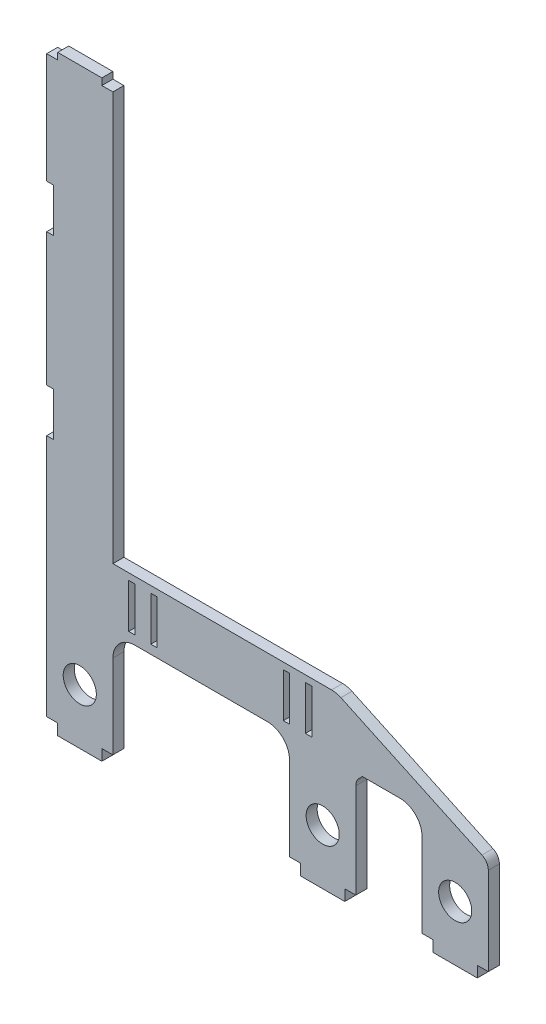
SolidWorks part; units mm, degrees
ref_plane "Front Plane" through (0, 0, 0) normal (0, 0, 1) x (1, 0, 0)
ref_plane "Top Plane" through (0, 0, 0) normal (0, 1, 0) x (1, 0, 0)
ref_plane "Right Plane" through (0, 0, 0) normal (1, 0, 0) x (0, 0, -1)
sketch "Sketch1" plane through (0, 0, 0) normal (0, 0, 1) x (1, 0, 0)
  line L0 (38.6, 72) -> (38.6, 52) construction
  line L1 (48.6, 72) -> (48.6, 52) construction
  line L2 (108.6, 72) -> (108.6, 52) construction
  line L3 (118.6, 72) -> (118.6, 52) construction
  line L4 (155, 62.0711) -> (155, 65.5389)
  line L5 (150.5677, 70.5065) -> (34.4323, 83.7792)
  line L6 (30, 88.7468) -> (30, 260)
  line L7 (30, 260) -> (25, 260)
  line L8 (25, 260) -> (25, 263)
  line L9 (25, 263) -> (5, 263)
  line L10 (5, 263) -> (5, 260)
  line L11 (5, 260) -> (0, 260)
  line L12 (0, 260) -> (0, 0)
  line L13 (0, 0) -> (5, 0)
  line L14 (5, 0) -> (5, -5)
  line L15 (5, -5) -> (25, -5)
  line L16 (25, -5) -> (25, 0)
  line L17 (25, 0) -> (30, 0)
  line L18 (30, 0) -> (30, 40)
  line L19 (35, 45) -> (105, 45)
  line L20 (110, 40) -> (110, 0)
  line L21 (110, 0) -> (115, 0)
  line L22 (115, 0) -> (115, -5)
  line L23 (115, -5) -> (135, -5)
  line L24 (135, -5) -> (135, 0)
  line L25 (135, 0) -> (140, 0)
  line L26 (140, 0) -> (140, 42.9289)
  line L27 (141.4645, 46.4645) -> (153.5355, 58.5355)
  line L28 (40.05, 52) -> (37.15, 52)
  line L29 (40.05, 72) -> (40.05, 52)
  line L30 (37.15, 52) -> (37.15, 72)
  line L31 (37.15, 72) -> (40.05, 72)
  line L32 (47.15, 72) -> (50.05, 72)
  line L33 (47.15, 52) -> (47.15, 72)
  line L34 (50.05, 72) -> (50.05, 52)
  line L35 (50.05, 52) -> (47.15, 52)
  line L36 (117.15, 72) -> (120.05, 72)
  line L37 (120.05, 72) -> (120.05, 52)
  line L38 (120.05, 52) -> (117.15, 52)
  line L39 (117.15, 52) -> (117.15, 72)
  line L40 (110.05, 52) -> (107.15, 52)
  line L41 (110.05, 72) -> (110.05, 52)
  line L42 (107.15, 52) -> (107.15, 72)
  line L43 (107.15, 72) -> (110.05, 72)
  arc A0 (155, 65.5389) -> (150.5677, 70.5065) centre (150, 65.5389) ccw
  arc A1 (30, 88.7468) -> (34.4323, 83.7792) centre (35, 88.7468) ccw
  arc A2 (35, 45) -> (30, 40) centre (35, 40) ccw
  arc A3 (110, 40) -> (105, 45) centre (105, 40) ccw
  arc A4 (141.4645, 46.4645) -> (140, 42.9289) centre (145, 42.9289) ccw
  arc A5 (153.5355, 58.5355) -> (155, 62.0711) centre (150, 62.0711) ccw
  point P63 (39.2533, 51.8883)
  dimension "D20" = 260
  dimension "D21" = 5
  dimension "D23" = 5
  dimension "D24" = 5
  dimension "D25" = 5
  dimension "D26" = 5
  dimension "D27" = 5
  dimension "D1" = 20
  dimension "D2" = 5
  dimension "D3" = 5
  dimension "D4" = 30
  dimension "D5" = 38.6
  dimension "D6" = 10
  dimension "D7" = 110
  dimension "D8" = 5
  dimension "D9" = 20
  dimension "D10" = 30
  dimension "D11" = 108.6
  dimension "D12" = 10
  dimension "D13" = 155
  dimension "D14" = 45
  dimension "D15" = 7
  dimension "D16" = 20
  dimension "D17" = 2.9
  dimension "D18" = 2.9
  dimension "D19" = 6.52
  dimension "D22" = 135
  dimension "D28" = 42.9289
  dimension "D29" = 3.4678
  dimension "D30" = 20
  dimension "D31" = 5
  dimension "D32" = 3
  dimension "D33" = 2.9
  dimension "D34" = 2.9
extrude "Boss-Extrude1" add sketch "Sketch1" along normal blind 5
sketch "Sketch2" plane through (0, 0, 5) normal (0, 0, 1) x (1, 0, 0)
  line L0 (30, 40) -> (30, 48)
  line L1 (30, 48) -> (110, 48)
  line L2 (110, 48) -> (110, 40)
  line L3 (35, 45) -> (105, 45) construction
  line L4 (35, 45) -> (105, 45)
  arc A0 (35, 45) -> (30, 40) centre (35, 40) ccw construction
  arc A1 (110, 40) -> (105, 45) centre (105, 40) ccw construction
  arc A2 (35, 45) -> (30, 40) centre (35, 40) ccw
  arc A3 (110, 40) -> (105, 45) centre (105, 40) ccw
  dimension "D1" = 3
extrude "Cut-Extrude1" cut sketch "Sketch2" against normal through all
fillet "Fillet1" radius 10 2 edges at (30, 48, 2.5) (110, 48, 2.5)
sketch "Sketch3" plane through (0, 0, 0) normal (0, 0, -1) x (-1, 0, 0)
  line L0 (0, 260) -> (0, 0) construction
  line L1 (0, 210) -> (-3, 210)
  line L2 (0, 210) -> (0, 190.2)
  line L3 (0, 190.2) -> (-3, 190.2)
  line L4 (-3, 210) -> (-3, 190.2)
  line L6 (-5, 260) -> (0, 260) construction
  dimension "D1" = 3
  dimension "D2" = 19.8
  dimension "D3" = 50
extrude "Cut-Extrude2" cut sketch "Sketch3" against normal blind 5
pattern_linear "LPattern1" count 2 spacing 80 along (0, -1, 0) of "Cut-Extrude2"
sketch "Sketch4" plane through (0, 0, 5) normal (0, 0, 1) x (1, 0, 0)
  line L0 (30, 88.7468) -> (30, 75)
  line L1 (30, 75) -> (111.25, 75)
  line L2 (150.5677, 70.5065) -> (34.4323, 83.7792) construction
  line L3 (111.25, 75) -> (34.4323, 83.7792)
  line L5 (50.05, 72) -> (47.15, 72) construction
  arc A0 (30, 88.7468) -> (34.4323, 83.7792) centre (35, 88.7468) ccw construction
  arc A1 (30, 88.7468) -> (34.4323, 83.7792) centre (35, 88.7468) ccw
  dimension "D1" = 3
extrude "Cut-Extrude3" cut sketch "Sketch4" against normal blind 10
sketch "Sketch5" plane through (0, 0, 5) normal (0, 0, 1) x (1, 0, 0)
  line L0 (111.25, 75) -> (131.25, 75)
  line L1 (131.25, 75) -> (153.5355, 58.5355)
  line L2 (141.4645, 46.4645) -> (153.5355, 58.5355) construction
  line L3 (111.25, 75) -> (134.91, 72.296)
  line L4 (150.5677, 70.5065) -> (111.25, 75) construction
  line L5 (155, 62.0711) -> (155, 65.5389) construction
  line L6 (150.5677, 70.5065) -> (111.25, 75)
  line L7 (155, 62.0711) -> (155, 65.5389)
  arc A0 (155, 65.5389) -> (150.5677, 70.5065) centre (150, 65.5389) ccw construction
  arc A1 (153.5355, 58.5355) -> (155, 62.0711) centre (150, 62.0711) ccw construction
  arc A2 (155, 65.5389) -> (150.5677, 70.5065) centre (150, 65.5389) ccw
  arc A3 (153.5355, 58.5355) -> (155, 62.0711) centre (150, 62.0711) ccw
  dimension "D1" = 20
extrude "Cut-Extrude4" cut sketch "Sketch5" against normal blind 5 contours L1 A3 L7 A2 L6 region at (147.9818, 66.6486, 5)
extrude "Boss-Extrude2" add sketch "Sketch5<3>" against normal blind 5 contours L0 L3 L1 region at (125.8033, 74.0987, 5)
sketch "Sketch5<3>" plane through (0, 0, 5) normal (0, 0, 1) x (1, 0, 0) same geometry as "Sketch5"
sketch "Sketch10" plane through (0, 0, 0) normal (0, 0, -1) x (-1, 0, 0)
  line L0 (-131.25, 75) -> (-200, 42.9413)
  line L1 (-200, 42.9413) -> (-200, 0)
  line L2 (-200, 0) -> (-170, 0)
  line L4 (-170, 0) -> (-170, 48)
  line L6 (-170, 48) -> (-143, 48)
  line L7 (-141.4645, 46.4645) -> (-153.5355, 58.5355) construction
  line L8 (-30, 75) -> (-131.25, 75) construction
  line L10 (-30, 0) -> (-30, 38) construction
  line L11 (-143, 48) -> (-153.5355, 58.5355)
  line L12 (-153.5355, 58.5355) -> (-131.25, 75)
  line L13 (-100, 48) -> (-40, 48) construction
  line L15 (-25, 0) -> (-30, 0) construction
  dimension "D1" = 25
  dimension "D2" = 30
  dimension "D3" = 170
extrude "Boss-Extrude3" add sketch "Sketch10" against normal up to vertex (5 mm away) up to point (153.5355, 58.5355, 5)
fillet "Fillet3" radius 10 2 edges at (131.25, 75, 2.5) (170, 48, 2.5)
fillet "Fillet4" radius 5 1 edges at (200, 42.9413, 2.5)
sketch "Sketch12" plane through (0, 0, 5) normal (0, 0, 1) x (1, 0, 0)
  line L0 (200, 0) -> (170, 0) construction
  line L1 (175, 0) -> (195, 0)
  line L2 (175, 0) -> (175, -5)
  line L3 (175, -5) -> (195, -5)
  line L4 (195, 0) -> (195, -5)
  line L5 (170, 0) -> (170, 38) construction
  dimension "D1" = 5
  dimension "D2" = 20
  dimension "D3" = 5
extrude "Boss-Extrude4" add sketch "Sketch12" against normal up to vertex (5 mm away) up to point (200, 0, 0)
sketch "Sketch13" plane through (0, 0, 5) normal (0, 0, 1) x (1, 0, 0)
  line L0 (5, -5) -> (25, -5) construction
  line L1 (0, 110.2) -> (0, 0) construction
  line L2 (110, 38) -> (110, 0) construction
  line L3 (170, 0) -> (170, 38) construction
  circle A0 centre (15, 20) radius 7.5
  circle A1 centre (125, 20) radius 7.5
  circle A2 centre (185, 20) radius 7.5
  dimension "D1" = 15
  dimension "D2" = 25
  dimension "D3" = 15
  dimension "D4" = 15
  dimension "D5" = 15
extrude "Cut-Extrude6" cut sketch "Sketch13" against normal through all
